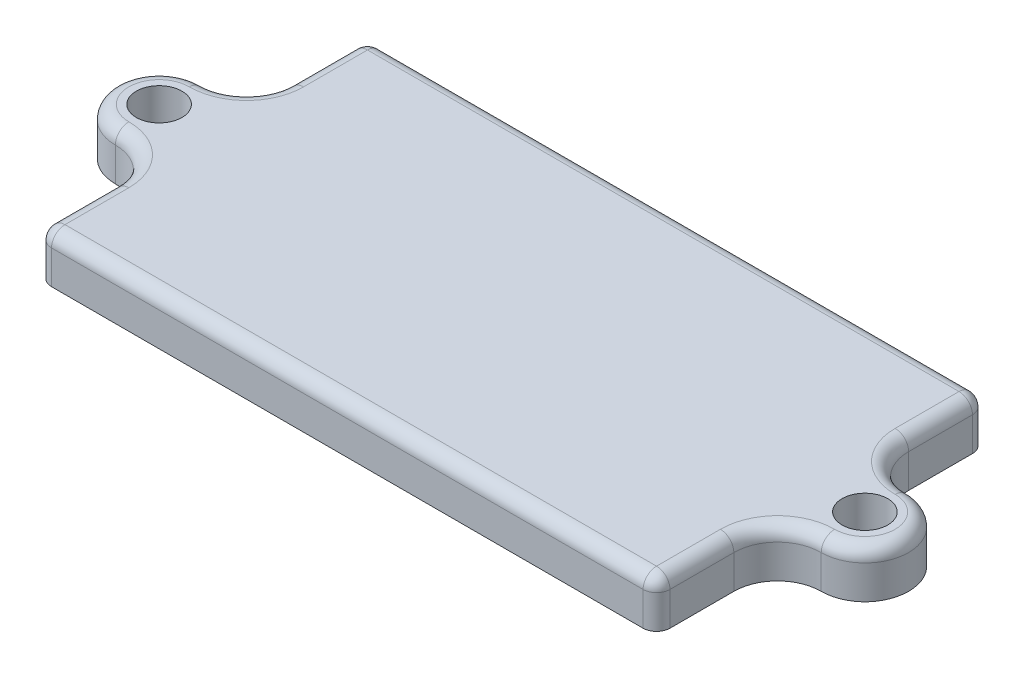
SolidWorks part; units mm, degrees
ref_plane "Спереди" through (0, 0, 0) normal (0, 0, 1) x (1, 0, 0)
ref_plane "Сверху" through (0, 0, 0) normal (0, 1, 0) x (1, 0, 0)
ref_plane "Справа" through (0, 0, 0) normal (1, 0, 0) x (0, 0, -1)
sketch "Эскиз1" plane through (0, 0, 0) normal (0, 1, 0) x (1, 0, 0)
  line L0 (-117.532, 0) -> (5759.069, 0) construction
  line L1 (0, -117.532) -> (0, 5759.069) construction
  line L2 (-10.75, -118.4842) -> (-10.75, 5758.1169) construction
  line L3 (22, -12.25) -> (-22, -12.25)
  line L4 (23, -11.25) -> (23, 11.25)
  line L5 (22, 12.25) -> (-22, 12.25)
  line L6 (-23, -11.25) -> (-23, 11.25)
  line L7 (23, -12.25) -> (-23, 12.25) construction
  line L8 (23, 12.25) -> (-23, -12.25) construction
  line L9 (10.75, -118.0956) -> (10.75, 5758.5055) construction
  line L10 (-1.5, 12.25) -> (-1.5, 9.25) construction
  line L11 (-20, 9.25) -> (-1.5, 9.25)
  line L12 (-20, 9.25) -> (-20, -9.25)
  line L13 (-20, -9.25) -> (-1.5, -9.25)
  line L14 (-1.5, 9.25) -> (-1.5, -9.25)
  line L15 (-20, 9.25) -> (-1.5, -9.25) construction
  line L16 (-20, -9.25) -> (-1.5, 9.25) construction
  line L17 (1.5, 9.25) -> (20, 9.25)
  line L18 (1.5, 9.25) -> (1.5, -9.25)
  line L19 (1.5, -9.25) -> (20, -9.25)
  line L20 (20, 9.25) -> (20, -9.25)
  line L21 (1.5, 9.25) -> (20, -9.25) construction
  line L22 (1.5, -9.25) -> (20, 9.25) construction
  line L23 (1.5, 9.25) -> (-1.5, 9.25) construction
  line L24 (20, 9.25) -> (23, 9.25) construction
  line L26 (-1.5, -12.25) -> (-11.5, -12.25)
  line L27 (-1.5, -12.25) -> (-1.5, -2.25)
  line L28 (-1.5, -2.25) -> (-11.5, -2.25)
  line L29 (-11.5, -12.25) -> (-11.5, -2.25)
  line L30 (20, -12.25) -> (10, -12.25)
  line L31 (20, -12.25) -> (20, -2.25)
  line L32 (20, -2.25) -> (10, -2.25)
  line L33 (10, -12.25) -> (10, -2.25)
  arc A0 (-26.25, 3.25) -> (-26.25, -3.25) centre (-26.25, 0) ccw
  circle A1 centre (-26.25, 0) radius 1.7
  arc A6 (-26.25, 3.25) -> (-23, 6.5) centre (-26.25, 6.5) ccw
  arc A7 (-23, -6.5) -> (-26.25, -3.25) centre (-26.25, -6.5) ccw
  circle A8 centre (26.25, 0) radius 1.7
  arc A9 (23, -6.5) -> (26.25, -3.25) centre (26.25, -6.5) cw
  arc A10 (26.25, 3.25) -> (23, 6.5) centre (26.25, 6.5) cw
  arc A11 (26.25, 3.25) -> (26.25, -3.25) centre (26.25, 0) cw
  arc A12 (-22, -12.25) -> (-23, -11.25) centre (-22, -11.25) cw
  arc A13 (22, -12.25) -> (23, -11.25) centre (22, -11.25) ccw
  arc A14 (23, 11.25) -> (22, 12.25) centre (22, 11.25) ccw
  arc A15 (-22, 12.25) -> (-23, 11.25) centre (-22, 11.25) ccw
  point P4 (0, 0)
  point P13 (-10.75, 0)
  point P19 (10.75, 0)
  point P24 (0, -12.25)
  point P25 (-10.75, 12.25)
  point P26 (10.75, 12.25)
  point P28 (0, 12.25)
  dimension "D3" = 3.4
  dimension "D4" = 6.5
  dimension "D6" = 1
  dimension "D1" = 24.5
  dimension "D2" = 18.5
  dimension "D5" = 10
extrude "Бобышка-Вытянуть1" add sketch "Эскиз1" along normal blind 1 contours A7 L6 A6 A0 A1 | L5 A15 L6 A12 L3 L29 L13 L12 L11 L14 L27 L33 L19 L18 L17 L20 L31 A13 L4 A14 | L29 L3 L27 L13 | L29 L13 L14 L28 | L13 L29 L28 L14 L11 L12 | L19 L33 L32 L20 L17 L18 | L33 L3 L31 L19 | L33 L19 L20 L32 | A11 A10 L4 A9 A8 region at (-0.6682, 0, -1.6901) region at (15, 0, 10.75) region at (15, 0, 5.75) region at (23.1453, 0, 0) region at (-6.5, 0, 10.75) region at (9.6573, 0, -1.4784) region at (-6.5, 0, 5.75) region at (-11.8427, 0, -1.4784) region at (-23.8491, 0, 4.0991)
extrude "Бобышка-Вытянуть2" add sketch "Эскиз1<3>" along normal blind 1 from surface contours L5 A15 L6 A12 L3 L29 L13 L12 L11 L14 L27 L33 L19 L18 L17 L20 L31 A13 L4 A14 | L13 L29 L28 L14 L11 L12 | A7 L6 A6 A0 A1 | L19 L33 L32 L20 L17 L18 | A11 A10 L4 A9 A8 region at (-0.6682, 0, -1.6901) region at (23.1453, 0, 0) region at (9.6573, 0, -1.4784) region at (-11.8427, 0, -1.4784) region at (-23.8491, 0, 4.0991) starting at face at (0, 1, 0)
sketch "Эскиз1<3>" plane through (0, 0, 0) normal (0, 1, 0) x (1, 0, 0) same geometry as "Эскиз1"
extrude "Бобышка-Вытянуть3" add sketch "Эскиз1<5>" along normal blind 3 from surface contours L5 A15 L6 A12 L3 L29 L13 L12 L11 L14 L27 L33 L19 L18 L17 L20 L31 A13 L4 A14 | A7 L6 A6 A0 A1 | A11 A10 L4 A9 A8 region at (-0.6682, 0, -1.6901) region at (23.1453, 0, 0) region at (-23.8491, 0, 4.0991) starting at face at (26.25, 2, 1.7)
sketch "Эскиз1<5>" plane through (0, 0, 0) normal (0, 1, 0) x (1, 0, 0) same geometry as "Эскиз1"
extrude "Бобышка-Вытянуть4" add sketch "Эскиз1<7>" along normal blind 2.5 from offset 7 separate body contours L5 A15 L6 A12 L3 L29 L13 L12 L11 L14 L27 L33 L19 L18 L17 L20 L31 A13 L4 A14 | A7 L6 A6 A0 A1 | A11 A10 L4 A9 A8 | L29 L3 L27 L13 | L33 L3 L31 L19 region at (-0.6682, 0, -1.6901) region at (15, 0, 10.75) region at (23.1453, 0, 0) region at (-6.5, 0, 10.75) region at (-23.8491, 0, 4.0991)
sketch "Эскиз1<7>" plane through (0, 0, 0) normal (0, 1, 0) x (1, 0, 0) same geometry as "Эскиз1"
extrude "Бобышка-Вытянуть5" add sketch "Эскиз1<9>" along normal blind 1 from surface contours L13 L29 L28 L14 L11 L12 | L19 L33 L32 L20 L17 L18 | L33 L19 L20 L32 | L33 L3 L31 L19 | L29 L3 L27 L13 | L29 L13 L14 L28 | L5 A15 L6 A12 L3 L29 L13 L12 L11 L14 L27 L33 L19 L18 L17 L20 L31 A13 L4 A14 | A11 A10 L4 A9 A8 | A7 L6 A6 A0 A1 region at (-0.6682, 0, -1.6901) region at (15, 0, 10.75) region at (15, 0, 5.75) region at (23.1453, 0, 0) region at (-6.5, 0, 10.75) region at (9.6573, 0, -1.4784) region at (-6.5, 0, 5.75) region at (-11.8427, 0, -1.4784) region at (-23.8491, 0, 4.0991) starting at face at (-10.75, 9.5, 0)
sketch "Эскиз1<9>" plane through (0, 0, 0) normal (0, 1, 0) x (1, 0, 0) same geometry as "Эскиз1"
fillet "Скругление1" radius 1 15 edges at (-22.7071, 10.5, 11.9571) (-23, 10.5, 8.875) (-23.9519, 10.5, 4.2019) (-29.5, 10.5, 0) (-23.9519, 10.5, -4.2019) (-22.7071, 10.5, -11.9571) (0, 10.5, -12.25) (22.7071, 10.5, -11.9571) (23, 10.5, -8.875) (23.9519, 10.5, -4.2019) (29.5, 10.5, 0) (23.9519, 10.5, 4.2019) (23, 10.5, 8.875) (22.7071, 10.5, 11.9571) (0, 10.5, 12.25)
delete or keep bodies "Тело-Удалить/Сохранить 2" type keep bodies bodies 105
